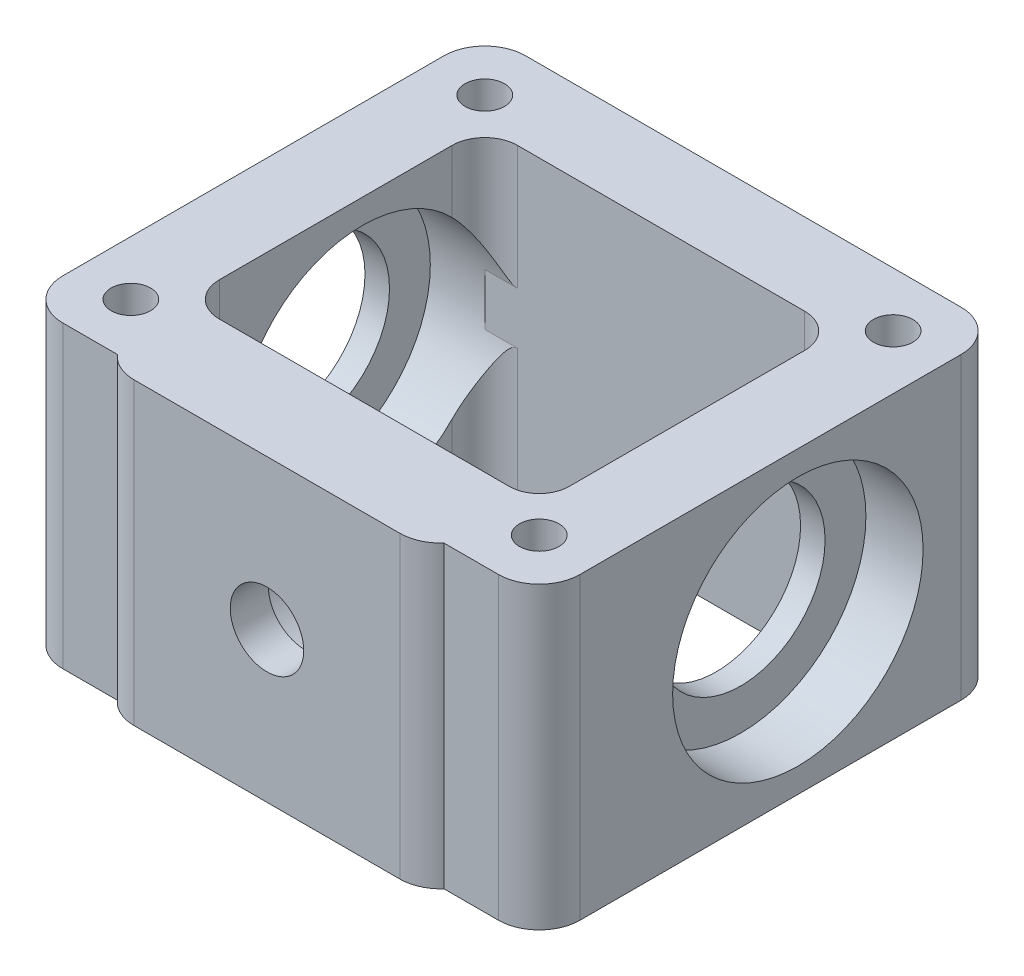
SolidWorks part; units mm, degrees
ref_plane "Front" through (0, 0, 0) normal (0, 0, 1) x (1, 0, 0)
ref_plane "Top" through (0, 0, 0) normal (0, 1, 0) x (1, 0, 0)
ref_plane "Right" through (0, 0, 0) normal (1, 0, 0) x (0, 0, -1)
sketch "Sketch3" plane through (0, 0, 0) normal (0, 1, 0) x (1, 0, 0)
  line L0 (6, -6) -> (32, -6)
  line L1 (0, 0) -> (38, 0)
  line L2 (0, 0) -> (0, -34)
  line L3 (0, -34) -> (38, -34)
  line L4 (38, 0) -> (38, -34)
  line L5 (32, -6) -> (32, -28)
  line L6 (6, -28) -> (32, -28)
  line L7 (6, -6) -> (6, -28)
  dimension "D1" = 38
  dimension "D2" = 34
  dimension "D3" = 6
extrude "Boss-Extrude1" add sketch "Sketch3" along normal blind 22
sketch "Sketch4" plane through (0, 0, 34) normal (0, 0, 1) x (1, 0, 0)
  line L0 (0, 0) -> (38, 0) construction
  line L1 (31, 0) -> (7, 0)
  line L2 (31, 0) -> (31, 22)
  line L3 (31, 22) -> (7, 22)
  line L4 (7, 0) -> (7, 22)
  line L5 (0, 22) -> (38, 22) construction
  dimension "D1" = 24
  dimension "D2" = 7
extrude "Boss-Extrude2" add sketch "Sketch4" along normal blind 1
sketch "Sketch5" plane through (0, 0, 35) normal (0, 0, 1) x (1, 0, 0)
  line L0 (31, 0) -> (31, 22) construction
  line L1 (7, 0) -> (31, 0) construction
  circle A0 centre (19, 11) radius 2.7
  dimension "D3" = 5.4
  dimension "D1" = 12
  dimension "D2" = 11
extrude "Cut-Extrude1" cut sketch "Sketch5" against normal blind 12
sketch "Sketch7" plane through (0, 0, 28) normal (0, 0, -1) x (-1, 0, 0)
  circle A0 centre (-19, 11) radius 5.7
  dimension "D1" = 11.4
extrude "Cut-Extrude3" cut sketch "Sketch7" against normal blind 4.2
sketch "Sketch8" plane through (38, 0, 0) normal (1, 0, 0) x (0, 0, -1)
  line L0 (0, 22) -> (0, 0) construction
  line L1 (-34, 0) -> (0, 0) construction
  circle A0 centre (-15, 11) radius 6.2
  dimension "D1" = 12.4
  dimension "D2" = 15
  dimension "D3" = 11
extrude "Cut-Extrude4" cut sketch "Sketch8" against normal through all
sketch "Sketch9" plane through (6, 0, 0) normal (1, 0, 0) x (0, 0, -1)
  circle A0 centre (-15, 11) radius 9.2
  dimension "D1" = 18.4
extrude "Cut-Extrude5" cut sketch "Sketch9" against normal blind 4.2
sketch "Sketch10" plane through (38, 0, 0) normal (1, 0, 0) x (0, 0, -1)
  circle A0 centre (-15, 11) radius 9.2
  dimension "D1" = 18.4
extrude "Cut-Extrude6" cut sketch "Sketch10" against normal blind 4.2
sketch "Sketch15" plane through (0, 0, 0) normal (0, -1, 0) x (-1, 0, 0)
  line L0 (0, 0) -> (0, -34) construction
  line L1 (0, -34) -> (-7, -34) construction
  circle A0 centre (-4, -30) radius 1.45
  circle A1 centre (-34, -30) radius 1.45
  circle A2 centre (-34, -4) radius 1.45
  circle A3 centre (-4, -4) radius 1.45
  dimension "D1" = 2.9
  dimension "D2" = 4
  dimension "D3" = 4
  dimension "D4" = 2
  dimension "D5" = 2
extrude "Cut-Extrude7" cut sketch "Sketch15" against normal through all
fillet "Fillet1" radius 3 6 edges at (38, 11, 0) (7, 11, 35) (0, 11, 34) (0, 11, 0) (31, 11, 35) (38, 11, 34)
fillet "Fillet3" radius 2.5 2 edges at (32, 11, 6) (6, 11, 28)
fillet "Fillet4" radius 2.2 1 edges at (32, 11, 28)
fillet "Fillet5" radius 2.4 2 edges at (6, 4.5461, 6) (6, 17.4539, 6)
